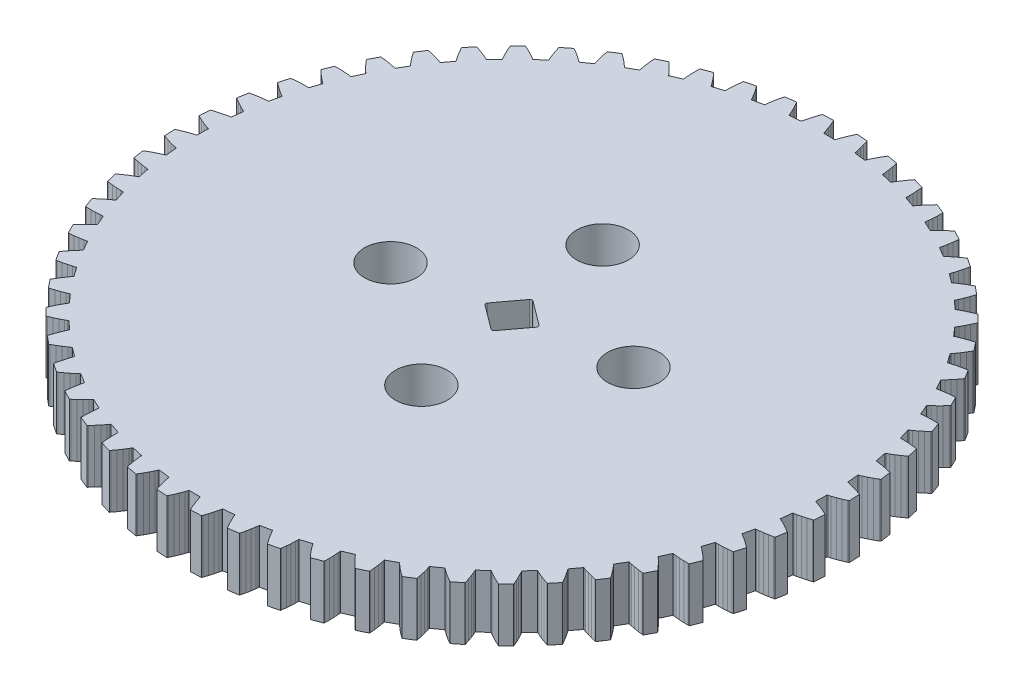
SolidWorks part; units mm, degrees
ref_plane "Front Plane" through (0, 0, 0) normal (0, 0, 1) x (1, 0, 0)
ref_plane "Top Plane" through (0, 0, 0) normal (0, 1, 0) x (1, 0, 0)
ref_plane "Right Plane" through (0, 0, 0) normal (1, 0, 0) x (0, 0, -1)
sketch "Sketch2" plane through (0, 0, 0) normal (0, 1, 0) x (1, 0, 0)
  line L0 (1.5877, 28.5868) -> (1.4918, 28.6064)
  line L1 (1.4918, 28.6064) -> (1.2998, 28.6492)
  line L2 (1.2998, 28.6492) -> (0.9152, 28.7484)
  line L3 (0.9152, 28.7484) -> (0.53, 28.8645)
  line L4 (0.53, 28.8645) -> (0.1446, 28.9962)
  line L5 (0.1446, 28.9962) -> (0.0483, 29.0314)
  line L6 (0.0483, 29.0314) -> (0.0085, 30.0293)
  line L7 (0.0085, 30.0293) -> (0.1018, 30.0721)
  line L8 (0.1018, 30.0721) -> (0.4755, 30.234)
  line L9 (0.4755, 30.234) -> (0.8502, 30.3803)
  line L10 (0.8502, 30.3803) -> (1.2257, 30.5098)
  line L11 (1.2257, 30.5098) -> (1.4137, 30.5678)
  line L12 (1.4137, 30.5678) -> (1.5078, 30.5949)
  line L13 (1.5078, 30.5949) -> (1.521, 31.6473)
  line L14 (1.521, 31.6473) -> (1.4277, 31.6768)
  line L15 (1.4277, 31.6768) -> (1.2412, 31.7395)
  line L16 (1.2412, 31.7395) -> (0.869, 31.8784)
  line L17 (0.869, 31.8784) -> (0.4981, 32.034)
  line L18 (0.4981, 32.034) -> (0.1286, 32.2053)
  line L19 (0.1286, 32.2053) -> (0.0365, 32.2505)
  line L20 (0.0365, 32.2505) -> (0.1012, 33.247)
  line L21 (0.1012, 33.247) -> (0.1984, 33.2798)
  line L22 (0.1984, 33.2798) -> (0.587, 33.4018)
  line L23 (0.587, 33.4018) -> (0.975, 33.5081)
  line L24 (0.975, 33.5081) -> (1.362, 33.5977)
  line L25 (1.362, 33.5977) -> (1.555, 33.6356)
  line L26 (1.555, 33.6356) -> (1.6514, 33.6528)
  line L27 (1.6514, 33.6528) -> (1.7745, 34.6981)
  line L28 (1.7745, 34.6981) -> (1.6848, 34.7372)
  line L29 (1.6848, 34.7372) -> (1.5059, 34.819)
  line L30 (1.5059, 34.819) -> (1.1503, 34.996)
  line L31 (1.1503, 34.996) -> (0.7977, 35.1896)
  line L32 (0.7977, 35.1896) -> (0.4481, 35.3986)
  line L33 (0.4481, 35.3986) -> (0.3612, 35.4531)
  line L34 (0.3612, 35.4531) -> (0.5298, 36.4374)
  line L35 (0.5298, 36.4374) -> (0.6299, 36.4599)
  line L36 (0.6299, 36.4599) -> (1.0291, 36.5406)
  line L37 (1.0291, 36.5406) -> (1.4261, 36.6058)
  line L38 (1.4261, 36.6058) -> (1.8203, 36.6544)
  line L39 (1.8203, 36.6544) -> (2.0162, 36.672)
  line L40 (2.0162, 36.672) -> (2.1139, 36.679)
  line L41 (2.1139, 36.679) -> (2.3456, 37.7056)
  line L42 (2.3456, 37.7056) -> (2.2604, 37.7539)
  line L43 (2.2604, 37.7539) -> (2.0911, 37.8539)
  line L44 (2.0911, 37.8539) -> (1.7559, 38.0672)
  line L45 (1.7559, 38.0672) -> (1.4255, 38.2965)
  line L46 (1.4255, 38.2965) -> (1.0996, 38.5409)
  line L47 (1.0996, 38.5409) -> (1.0189, 38.6042)
  line L48 (1.0189, 38.6042) -> (1.2894, 39.5655)
  line L49 (1.2894, 39.5655) -> (1.3914, 39.5774)
  line L50 (1.3914, 39.5774) -> (1.7968, 39.6159)
  line L51 (1.7968, 39.6159) -> (2.1984, 39.6393)
  line L52 (2.1984, 39.6393) -> (2.5956, 39.6464)
  line L53 (2.5956, 39.6464) -> (2.7923, 39.6434)
  line L54 (2.7923, 39.6434) -> (2.8901, 39.6402)
  line L55 (2.8901, 39.6402) -> (3.2279, 40.637)
  line L56 (3.2279, 40.637) -> (3.1482, 40.6939)
  line L57 (3.1482, 40.6939) -> (2.9903, 40.8111)
  line L58 (2.9903, 40.8111) -> (2.6792, 41.0582)
  line L59 (2.6792, 41.0582) -> (2.3746, 41.3209)
  line L60 (2.3746, 41.3209) -> (2.0761, 41.5979)
  line L61 (2.0761, 41.5979) -> (2.0024, 41.6694)
  line L62 (2.0024, 41.6694) -> (2.372, 42.5971)
  line L63 (2.372, 42.5971) -> (2.4746, 42.5983)
  line L64 (2.4746, 42.5983) -> (2.8818, 42.5942)
  line L65 (2.8818, 42.5942) -> (3.2836, 42.5754)
  line L66 (3.2836, 42.5754) -> (3.6794, 42.541)
  line L67 (3.6794, 42.541) -> (3.8747, 42.5175)
  line L68 (3.8747, 42.5175) -> (3.9716, 42.504)
  line L69 (3.9716, 42.504) -> (4.4118, 43.4601)
  line L70 (4.4118, 43.4601) -> (4.3385, 43.525)
  line L71 (4.3385, 43.525) -> (4.1936, 43.6581)
  line L72 (4.1936, 43.6581) -> (3.9102, 43.9363)
  line L73 (3.9102, 43.9363) -> (3.6346, 44.2294)
  line L74 (3.6346, 44.2294) -> (3.3667, 44.5362)
  line L75 (3.3667, 44.5362) -> (3.3009, 44.6149)
  line L76 (3.3009, 44.6149) -> (3.7654, 45.4989)
  line L77 (3.7654, 45.4989) -> (3.8676, 45.4893)
  line L78 (3.8676, 45.4893) -> (4.2722, 45.4427)
  line L79 (4.2722, 45.4427) -> (4.6698, 45.3821)
  line L80 (4.6698, 45.3821) -> (5.0598, 45.3065)
  line L81 (5.0598, 45.3065) -> (5.2516, 45.2627)
  line L82 (5.2516, 45.2627) -> (5.3466, 45.2391)
  line L83 (5.3466, 45.2391) -> (5.8842, 46.1439)
  line L84 (5.8842, 46.1439) -> (5.8182, 46.2162)
  line L85 (5.8182, 46.2162) -> (5.688, 46.3637)
  line L86 (5.688, 46.3637) -> (5.4352, 46.67)
  line L87 (5.4352, 46.67) -> (5.1918, 46.9903)
  line L88 (5.1918, 46.9903) -> (4.9574, 47.3234)
  line L89 (4.9574, 47.3234) -> (4.9002, 47.4085)
  line L90 (4.9002, 47.4085) -> (5.4545, 48.2392)
  line L91 (5.4545, 48.2392) -> (5.5552, 48.219)
  line L92 (5.5552, 48.219) -> (5.9527, 48.1303)
  line L93 (5.9527, 48.1303) -> (6.3418, 48.0284)
  line L94 (6.3418, 48.0284) -> (6.7217, 47.9125)
  line L95 (6.7217, 47.9125) -> (6.9079, 47.8489)
  line L96 (6.9079, 47.8489) -> (6.9999, 47.8156)
  line L97 (6.9999, 47.8156) -> (7.6292, 48.6592)
  line L98 (7.6292, 48.6592) -> (7.571, 48.7379)
  line L99 (7.571, 48.7379) -> (7.457, 48.8982)
  line L100 (7.457, 48.8982) -> (7.2376, 49.2293)
  line L101 (7.2376, 49.2293) -> (7.029, 49.5733)
  line L102 (7.029, 49.5733) -> (6.8307, 49.929)
  line L103 (6.8307, 49.929) -> (6.7827, 50.0197)
  line L104 (6.7827, 50.0197) -> (7.4209, 50.7878)
  line L105 (7.4209, 50.7878) -> (7.5188, 50.7573)
  line L106 (7.5188, 50.7573) -> (7.9049, 50.6275)
  line L107 (7.9049, 50.6275) -> (8.2812, 50.4855)
  line L108 (8.2812, 50.4855) -> (8.647, 50.3305)
  line L109 (8.647, 50.3305) -> (8.8254, 50.2478)
  line L110 (8.8254, 50.2478) -> (8.9135, 50.205)
  line L111 (8.9135, 50.205) -> (9.6275, 50.9783)
  line L112 (9.6275, 50.9783) -> (9.5779, 51.0626)
  line L113 (9.5779, 51.0626) -> (9.4812, 51.234)
  line L114 (9.4812, 51.234) -> (9.2976, 51.5862)
  line L115 (9.2976, 51.5862) -> (9.1262, 51.9501)
  line L116 (9.1262, 51.9501) -> (8.9662, 52.3246)
  line L117 (8.9662, 52.3246) -> (8.9279, 52.4198)
  line L118 (8.9279, 52.4198) -> (9.6428, 53.117)
  line L119 (9.6428, 53.117) -> (9.737, 53.0764)
  line L120 (9.737, 53.0764) -> (10.1075, 52.907)
  line L121 (10.1075, 52.907) -> (10.4669, 52.7265)
  line L122 (10.4669, 52.7265) -> (10.8144, 52.534)
  line L123 (10.8144, 52.534) -> (10.9833, 52.4331)
  line L124 (10.9833, 52.4331) -> (11.0664, 52.3814)
  line L125 (11.0664, 52.3814) -> (11.8573, 53.0757)
  line L126 (11.8573, 53.0757) -> (11.8168, 53.1649)
  line L127 (11.8168, 53.1649) -> (11.7386, 53.3454)
  line L128 (11.7386, 53.3454) -> (11.5928, 53.7148)
  line L129 (11.5928, 53.7148) -> (11.4603, 54.0947)
  line L130 (11.4603, 54.0947) -> (11.3403, 54.4839)
  line L131 (11.3403, 54.4839) -> (11.3122, 54.5826)
  line L132 (11.3122, 54.5826) -> (12.0961, 55.2012)
  line L133 (12.0961, 55.2012) -> (12.1855, 55.1509)
  line L134 (12.1855, 55.1509) -> (12.5362, 54.9438)
  line L135 (12.5362, 54.9438) -> (12.8748, 54.7266)
  line L136 (12.8748, 54.7266) -> (13.2003, 54.499)
  line L137 (13.2003, 54.499) -> (13.3577, 54.3809)
  line L138 (13.3577, 54.3809) -> (13.4349, 54.3208)
  line L139 (13.4349, 54.3208) -> (14.2941, 54.9287)
  line L140 (14.2941, 54.9287) -> (14.2631, 55.0215)
  line L141 (14.2631, 55.0215) -> (14.2042, 55.2092)
  line L142 (14.2042, 55.2092) -> (14.0978, 55.5919)
  line L143 (14.0978, 55.5919) -> (14.0058, 55.9835)
  line L144 (14.0058, 55.9835) -> (13.9271, 56.3831)
  line L145 (13.9271, 56.3831) -> (13.9095, 56.4842)
  line L146 (13.9095, 56.4842) -> (14.7538, 57.0175)
  line L147 (14.7538, 57.0175) -> (14.8375, 56.9582)
  line L148 (14.8375, 56.9582) -> (15.1646, 56.7155)
  line L149 (15.1646, 56.7155) -> (15.4786, 56.4641)
  line L150 (15.4786, 56.4641) -> (15.7785, 56.2037)
  line L151 (15.7785, 56.2037) -> (15.9227, 56.0699)
  line L152 (15.9227, 56.0699) -> (15.9932, 56.002)
  line L153 (15.9932, 56.002) -> (16.9112, 56.5167)
  line L154 (16.9112, 56.5167) -> (16.8901, 56.6123)
  line L155 (16.8901, 56.6123) -> (16.8512, 56.8051)
  line L156 (16.8512, 56.8051) -> (16.7854, 57.1969)
  line L157 (16.7854, 57.1969) -> (16.7347, 57.5959)
  line L158 (16.7347, 57.5959) -> (16.6983, 58.0016)
  line L159 (16.6983, 58.0016) -> (16.6913, 58.104)
  line L160 (16.6913, 58.104) -> (17.5867, 58.5461)
  line L161 (17.5867, 58.5461) -> (17.6638, 58.4783)
  line L162 (17.6638, 58.4783) -> (17.9637, 58.2028)
  line L163 (17.9637, 58.2028) -> (18.2498, 57.92)
  line L164 (18.2498, 57.92) -> (18.5208, 57.6296)
  line L165 (18.5208, 57.6296) -> (18.6502, 57.4814)
  line L166 (18.6502, 57.4814) -> (18.7133, 57.4066)
  line L167 (18.7133, 57.4066) -> (19.6801, 57.8225)
  line L168 (19.6801, 57.8225) -> (19.6691, 57.9198)
  line L169 (19.6691, 57.9198) -> (19.6504, 58.1156)
  line L170 (19.6504, 58.1156) -> (19.626, 58.5121)
  line L171 (19.626, 58.5121) -> (19.6173, 58.9143)
  line L172 (19.6173, 58.9143) -> (19.6235, 59.3215)
  line L173 (19.6235, 59.3215) -> (19.6273, 59.4241)
  line L174 (19.6273, 59.4241) -> (20.5639, 59.7702)
  line L175 (20.5639, 59.7702) -> (20.6335, 59.6947)
  line L176 (20.6335, 59.6947) -> (20.903, 59.3893)
  line L177 (20.903, 59.3893) -> (21.1579, 59.0782)
  line L178 (21.1579, 59.0782) -> (21.3971, 58.7611)
  line L179 (21.3971, 58.7611) -> (21.5103, 58.6002)
  line L180 (21.5103, 58.6002) -> (21.5652, 58.5191)
  line L181 (21.5652, 58.5191) -> (22.5702, 58.8317)
  line L182 (22.5702, 58.8317) -> (22.5694, 58.9296)
  line L183 (22.5694, 58.9296) -> (22.5714, 59.1264)
  line L184 (22.5714, 59.1264) -> (22.5885, 59.5232)
  line L185 (22.5885, 59.5232) -> (22.6219, 59.9241)
  line L186 (22.6219, 59.9241) -> (22.6706, 60.3284)
  line L187 (22.6706, 60.3284) -> (22.6851, 60.43)
  line L188 (22.6851, 60.43) -> (23.6528, 60.6763)
  line L189 (23.6528, 60.6763) -> (23.7141, 60.594)
  line L190 (23.7141, 60.594) -> (23.9502, 60.2621)
  line L191 (23.9502, 60.2621) -> (24.1712, 59.926)
  line L192 (24.1712, 59.926) -> (24.3759, 59.5857)
  line L193 (24.3759, 59.5857) -> (24.4717, 59.4138)
  line L194 (24.4717, 59.4138) -> (24.5178, 59.3275)
  line L195 (24.5178, 59.3275) -> (25.55, 59.5333)
  line L196 (25.55, 59.5333) -> (25.5594, 59.6308)
  line L197 (25.5594, 59.6308) -> (25.5819, 59.8262)
  line L198 (25.5819, 59.8262) -> (25.6404, 60.2191)
  line L199 (25.6404, 60.2191) -> (25.7156, 60.6143)
  line L200 (25.7156, 60.6143) -> (25.8063, 61.0113)
  line L201 (25.8063, 61.0113) -> (25.8313, 61.1108)
  line L202 (25.8313, 61.1108) -> (26.8195, 61.2547)
  line L203 (26.8195, 61.2547) -> (26.8718, 61.1664)
  line L204 (26.8718, 61.1664) -> (27.0719, 60.8117)
  line L205 (27.0719, 60.8117) -> (27.2566, 60.4543)
  line L206 (27.2566, 60.4543) -> (27.4246, 60.0944)
  line L207 (27.4246, 60.0944) -> (27.5019, 59.9135)
  line L208 (27.5019, 59.9135) -> (27.5388, 59.8228)
  line L209 (27.5388, 59.8228) -> (28.5868, 59.9196)
  line L210 (28.5868, 59.9196) -> (28.6064, 60.0155)
  line L211 (28.6064, 60.0155) -> (28.6492, 60.2075)
  line L212 (28.6492, 60.2075) -> (28.7484, 60.5922)
  line L213 (28.7484, 60.5922) -> (28.8645, 60.9773)
  line L214 (28.8645, 60.9773) -> (28.9962, 61.3627)
  line L215 (28.9962, 61.3627) -> (29.0314, 61.4591)
  line L216 (29.0314, 61.4591) -> (30.0293, 61.4988)
  line L217 (30.0293, 61.4988) -> (30.0721, 61.4055)
  line L218 (30.0721, 61.4055) -> (30.234, 61.0318)
  line L219 (30.234, 61.0318) -> (30.3803, 60.6571)
  line L220 (30.3803, 60.6571) -> (30.5098, 60.2816)
  line L221 (30.5098, 60.2816) -> (30.5678, 60.0936)
  line L222 (30.5678, 60.0936) -> (30.5949, 59.9996)
  line L223 (30.5949, 59.9996) -> (31.6473, 59.9863)
  line L224 (31.6473, 59.9863) -> (31.6768, 60.0797)
  line L225 (31.6768, 60.0797) -> (31.7395, 60.2662)
  line L226 (31.7395, 60.2662) -> (31.8784, 60.6383)
  line L227 (31.8784, 60.6383) -> (32.034, 61.0092)
  line L228 (32.034, 61.0092) -> (32.2053, 61.3787)
  line L229 (32.2053, 61.3787) -> (32.2505, 61.4709)
  line L230 (32.2505, 61.4709) -> (33.247, 61.4061)
  line L231 (33.247, 61.4061) -> (33.2798, 61.3089)
  line L232 (33.2798, 61.3089) -> (33.4018, 60.9203)
  line L233 (33.4018, 60.9203) -> (33.5081, 60.5323)
  line L234 (33.5081, 60.5323) -> (33.5977, 60.1454)
  line L235 (33.5977, 60.1454) -> (33.6356, 59.9523)
  line L236 (33.6356, 59.9523) -> (33.6528, 59.8559)
  line L237 (33.6528, 59.8559) -> (34.6981, 59.7328)
  line L238 (34.6981, 59.7328) -> (34.7372, 59.8225)
  line L239 (34.7372, 59.8225) -> (34.819, 60.0014)
  line L240 (34.819, 60.0014) -> (34.996, 60.357)
  line L241 (34.996, 60.357) -> (35.1896, 60.7096)
  line L242 (35.1896, 60.7096) -> (35.3986, 61.0592)
  line L243 (35.3986, 61.0592) -> (35.4531, 61.1462)
  line L244 (35.4531, 61.1462) -> (36.4374, 60.9776)
  line L245 (36.4374, 60.9776) -> (36.4599, 60.8774)
  line L246 (36.4599, 60.8774) -> (36.5406, 60.4782)
  line L247 (36.5406, 60.4782) -> (36.6058, 60.0813)
  line L248 (36.6058, 60.0813) -> (36.6544, 59.6871)
  line L249 (36.6544, 59.6871) -> (36.672, 59.4911)
  line L250 (36.672, 59.4911) -> (36.679, 59.3935)
  line L251 (36.679, 59.3935) -> (37.7056, 59.1617)
  line L252 (37.7056, 59.1617) -> (37.7539, 59.2469)
  line L253 (37.7539, 59.2469) -> (37.8539, 59.4163)
  line L254 (37.8539, 59.4163) -> (38.0672, 59.7514)
  line L255 (38.0672, 59.7514) -> (38.2965, 60.0819)
  line L256 (38.2965, 60.0819) -> (38.5409, 60.4077)
  line L257 (38.5409, 60.4077) -> (38.6042, 60.4884)
  line L258 (38.6042, 60.4884) -> (39.5655, 60.2179)
  line L259 (39.5655, 60.2179) -> (39.5774, 60.116)
  line L260 (39.5774, 60.116) -> (39.6159, 59.7105)
  line L261 (39.6159, 59.7105) -> (39.6393, 59.3089)
  line L262 (39.6393, 59.3089) -> (39.6464, 58.9118)
  line L263 (39.6464, 58.9118) -> (39.6434, 58.7151)
  line L264 (39.6434, 58.7151) -> (39.6402, 58.6172)
  line L265 (39.6402, 58.6172) -> (40.637, 58.2794)
  line L266 (40.637, 58.2794) -> (40.6939, 58.3591)
  line L267 (40.6939, 58.3591) -> (40.8111, 58.5171)
  line L268 (40.8111, 58.5171) -> (41.0582, 58.8281)
  line L269 (41.0582, 58.8281) -> (41.3209, 59.1328)
  line L270 (41.3209, 59.1328) -> (41.5979, 59.4313)
  line L271 (41.5979, 59.4313) -> (41.6694, 59.5049)
  line L272 (41.6694, 59.5049) -> (42.5971, 59.1354)
  line L273 (42.5971, 59.1354) -> (42.5983, 59.0328)
  line L274 (42.5983, 59.0328) -> (42.5942, 58.6255)
  line L275 (42.5942, 58.6255) -> (42.5754, 58.2237)
  line L276 (42.5754, 58.2237) -> (42.541, 57.828)
  line L277 (42.541, 57.828) -> (42.5175, 57.6327)
  line L278 (42.5175, 57.6327) -> (42.504, 57.5357)
  line L279 (42.504, 57.5357) -> (43.4601, 57.0956)
  line L280 (43.4601, 57.0956) -> (43.525, 57.1688)
  line L281 (43.525, 57.1688) -> (43.6581, 57.3137)
  line L282 (43.6581, 57.3137) -> (43.9363, 57.5972)
  line L283 (43.9363, 57.5972) -> (44.2294, 57.8727)
  line L284 (44.2294, 57.8727) -> (44.5362, 58.1406)
  line L285 (44.5362, 58.1406) -> (44.6149, 58.2064)
  line L286 (44.6149, 58.2064) -> (45.4989, 57.7419)
  line L287 (45.4989, 57.7419) -> (45.4893, 57.6398)
  line L288 (45.4893, 57.6398) -> (45.4427, 57.2351)
  line L289 (45.4427, 57.2351) -> (45.3821, 56.8375)
  line L290 (45.3821, 56.8375) -> (45.3065, 56.4475)
  line L291 (45.3065, 56.4475) -> (45.2627, 56.2558)
  line L292 (45.2627, 56.2558) -> (45.2391, 56.1607)
  line L293 (45.2391, 56.1607) -> (46.1439, 55.6231)
  line L294 (46.1439, 55.6231) -> (46.2162, 55.6892)
  line L295 (46.2162, 55.6892) -> (46.3637, 55.8193)
  line L296 (46.3637, 55.8193) -> (46.67, 56.0722)
  line L297 (46.67, 56.0722) -> (46.9903, 56.3156)
  line L298 (46.9903, 56.3156) -> (47.3234, 56.5499)
  line L299 (47.3234, 56.5499) -> (47.4085, 56.6072)
  line L300 (47.4085, 56.6072) -> (48.2392, 56.0528)
  line L301 (48.2392, 56.0528) -> (48.219, 55.9522)
  line L302 (48.219, 55.9522) -> (48.1303, 55.5547)
  line L303 (48.1303, 55.5547) -> (48.0284, 55.1655)
  line L304 (48.0284, 55.1655) -> (47.9125, 54.7856)
  line L305 (47.9125, 54.7856) -> (47.8489, 54.5995)
  line L306 (47.8489, 54.5995) -> (47.8156, 54.5074)
  line L307 (47.8156, 54.5074) -> (48.6592, 53.8781)
  line L308 (48.6592, 53.8781) -> (48.7379, 53.9363)
  line L309 (48.7379, 53.9363) -> (48.8982, 54.0503)
  line L310 (48.8982, 54.0503) -> (49.2293, 54.2698)
  line L311 (49.2293, 54.2698) -> (49.5733, 54.4783)
  line L312 (49.5733, 54.4783) -> (49.929, 54.6766)
  line L313 (49.929, 54.6766) -> (50.0197, 54.7246)
  line L314 (50.0197, 54.7246) -> (50.7878, 54.0865)
  line L315 (50.7878, 54.0865) -> (50.7573, 53.9885)
  line L316 (50.7573, 53.9885) -> (50.6275, 53.6024)
  line L317 (50.6275, 53.6024) -> (50.4855, 53.2261)
  line L318 (50.4855, 53.2261) -> (50.3305, 52.8604)
  line L319 (50.3305, 52.8604) -> (50.2478, 52.6819)
  line L320 (50.2478, 52.6819) -> (50.205, 52.5938)
  line L321 (50.205, 52.5938) -> (50.9783, 51.8798)
  line L322 (50.9783, 51.8798) -> (51.0626, 51.9294)
  line L323 (51.0626, 51.9294) -> (51.234, 52.0261)
  line L324 (51.234, 52.0261) -> (51.5862, 52.2097)
  line L325 (51.5862, 52.2097) -> (51.9501, 52.3812)
  line L326 (51.9501, 52.3812) -> (52.3246, 52.5412)
  line L327 (52.3246, 52.5412) -> (52.4198, 52.5795)
  line L328 (52.4198, 52.5795) -> (53.117, 51.8645)
  line L329 (53.117, 51.8645) -> (53.0764, 51.7703)
  line L330 (53.0764, 51.7703) -> (52.907, 51.3999)
  line L331 (52.907, 51.3999) -> (52.7265, 51.0404)
  line L332 (52.7265, 51.0404) -> (52.534, 50.6929)
  line L333 (52.534, 50.6929) -> (52.4331, 50.5241)
  line L334 (52.4331, 50.5241) -> (52.3814, 50.441)
  line L335 (52.3814, 50.441) -> (53.0757, 49.65)
  line L336 (53.0757, 49.65) -> (53.1649, 49.6906)
  line L337 (53.1649, 49.6906) -> (53.3454, 49.7688)
  line L338 (53.3454, 49.7688) -> (53.7148, 49.9146)
  line L339 (53.7148, 49.9146) -> (54.0947, 50.0471)
  line L340 (54.0947, 50.0471) -> (54.4839, 50.1671)
  line L341 (54.4839, 50.1671) -> (54.5826, 50.1952)
  line L342 (54.5826, 50.1952) -> (55.2012, 49.4113)
  line L343 (55.2012, 49.4113) -> (55.1509, 49.3218)
  line L344 (55.1509, 49.3218) -> (54.9438, 48.9711)
  line L345 (54.9438, 48.9711) -> (54.7266, 48.6325)
  line L346 (54.7266, 48.6325) -> (54.499, 48.307)
  line L347 (54.499, 48.307) -> (54.3809, 48.1497)
  line L348 (54.3809, 48.1497) -> (54.3208, 48.0724)
  line L349 (54.3208, 48.0724) -> (54.9287, 47.2132)
  line L350 (54.9287, 47.2132) -> (55.0215, 47.2442)
  line L351 (55.0215, 47.2442) -> (55.2092, 47.3031)
  line L352 (55.2092, 47.3031) -> (55.5919, 47.4095)
  line L353 (55.5919, 47.4095) -> (55.9835, 47.5016)
  line L354 (55.9835, 47.5016) -> (56.3831, 47.5802)
  line L355 (56.3831, 47.5802) -> (56.4842, 47.5979)
  line L356 (56.4842, 47.5979) -> (57.0175, 46.7536)
  line L357 (57.0175, 46.7536) -> (56.9582, 46.6699)
  line L358 (56.9582, 46.6699) -> (56.7155, 46.3428)
  line L359 (56.7155, 46.3428) -> (56.4641, 46.0287)
  line L360 (56.4641, 46.0287) -> (56.2037, 45.7288)
  line L361 (56.2037, 45.7288) -> (56.0699, 45.5846)
  line L362 (56.0699, 45.5846) -> (56.002, 45.5141)
  line L363 (56.002, 45.5141) -> (56.5167, 44.5961)
  line L364 (56.5167, 44.5961) -> (56.6123, 44.6172)
  line L365 (56.6123, 44.6172) -> (56.8051, 44.6562)
  line L366 (56.8051, 44.6562) -> (57.1969, 44.722)
  line L367 (57.1969, 44.722) -> (57.5959, 44.7726)
  line L368 (57.5959, 44.7726) -> (58.0016, 44.809)
  line L369 (58.0016, 44.809) -> (58.104, 44.816)
  line L370 (58.104, 44.816) -> (58.5461, 43.9206)
  line L371 (58.5461, 43.9206) -> (58.4783, 43.8436)
  line L372 (58.4783, 43.8436) -> (58.2028, 43.5436)
  line L373 (58.2028, 43.5436) -> (57.92, 43.2576)
  line L374 (57.92, 43.2576) -> (57.6296, 42.9865)
  line L375 (57.6296, 42.9865) -> (57.4814, 42.8571)
  line L376 (57.4814, 42.8571) -> (57.4066, 42.7941)
  line L377 (57.4066, 42.7941) -> (57.8225, 41.8273)
  line L378 (57.8225, 41.8273) -> (57.9198, 41.8383)
  line L379 (57.9198, 41.8383) -> (58.1156, 41.8569)
  line L380 (58.1156, 41.8569) -> (58.5121, 41.8814)
  line L381 (58.5121, 41.8814) -> (58.9143, 41.89)
  line L382 (58.9143, 41.89) -> (59.3215, 41.8839)
  line L383 (59.3215, 41.8839) -> (59.4241, 41.8801)
  line L384 (59.4241, 41.8801) -> (59.7702, 40.9434)
  line L385 (59.7702, 40.9434) -> (59.6947, 40.8738)
  line L386 (59.6947, 40.8738) -> (59.3893, 40.6043)
  line L387 (59.3893, 40.6043) -> (59.0782, 40.3494)
  line L388 (59.0782, 40.3494) -> (58.7611, 40.1102)
  line L389 (58.7611, 40.1102) -> (58.6002, 39.997)
  line L390 (58.6002, 39.997) -> (58.5191, 39.9421)
  line L391 (58.5191, 39.9421) -> (58.8317, 38.9372)
  line L392 (58.8317, 38.9372) -> (58.9296, 38.9379)
  line L393 (58.9296, 38.9379) -> (59.1264, 38.936)
  line L394 (59.1264, 38.936) -> (59.5232, 38.9189)
  line L395 (59.5232, 38.9189) -> (59.9241, 38.8854)
  line L396 (59.9241, 38.8854) -> (60.3284, 38.8367)
  line L397 (60.3284, 38.8367) -> (60.43, 38.8223)
  line L398 (60.43, 38.8223) -> (60.6763, 37.8545)
  line L399 (60.6763, 37.8545) -> (60.594, 37.7932)
  line L400 (60.594, 37.7932) -> (60.2621, 37.5571)
  line L401 (60.2621, 37.5571) -> (59.926, 37.3361)
  line L402 (59.926, 37.3361) -> (59.5857, 37.1314)
  line L403 (59.5857, 37.1314) -> (59.4138, 37.0356)
  line L404 (59.4138, 37.0356) -> (59.3275, 36.9895)
  line L405 (59.3275, 36.9895) -> (59.5333, 35.9574)
  line L406 (59.5333, 35.9574) -> (59.6308, 35.9479)
  line L407 (59.6308, 35.9479) -> (59.8262, 35.9254)
  line L408 (59.8262, 35.9254) -> (60.2191, 35.8669)
  line L409 (60.2191, 35.8669) -> (60.6143, 35.7918)
  line L410 (60.6143, 35.7918) -> (61.0113, 35.7011)
  line L411 (61.0113, 35.7011) -> (61.1108, 35.676)
  line L412 (61.1108, 35.676) -> (61.2547, 34.6878)
  line L413 (61.2547, 34.6878) -> (61.1664, 34.6355)
  line L414 (61.1664, 34.6355) -> (60.8117, 34.4354)
  line L415 (60.8117, 34.4354) -> (60.4543, 34.2507)
  line L416 (60.4543, 34.2507) -> (60.0944, 34.0827)
  line L417 (60.0944, 34.0827) -> (59.9135, 34.0054)
  line L418 (59.9135, 34.0054) -> (59.8228, 33.9686)
  line L419 (59.8228, 33.9686) -> (59.9196, 32.9206)
  line L420 (59.9196, 32.9206) -> (60.0155, 32.901)
  line L421 (60.0155, 32.901) -> (60.2075, 32.8582)
  line L422 (60.2075, 32.8582) -> (60.5922, 32.7589)
  line L423 (60.5922, 32.7589) -> (60.9773, 32.6429)
  line L424 (60.9773, 32.6429) -> (61.3627, 32.5112)
  line L425 (61.3627, 32.5112) -> (61.4591, 32.4759)
  line L426 (61.4591, 32.4759) -> (61.4988, 31.4781)
  line L427 (61.4988, 31.4781) -> (61.4055, 31.4352)
  line L428 (61.4055, 31.4352) -> (61.0318, 31.2733)
  line L429 (61.0318, 31.2733) -> (60.6571, 31.127)
  line L430 (60.6571, 31.127) -> (60.2816, 30.9975)
  line L431 (60.2816, 30.9975) -> (60.0936, 30.9396)
  line L432 (60.0936, 30.9396) -> (59.9996, 30.9124)
  line L433 (59.9996, 30.9124) -> (59.9863, 29.86)
  line L434 (59.9863, 29.86) -> (60.0797, 29.8305)
  line L435 (60.0797, 29.8305) -> (60.2662, 29.7678)
  line L436 (60.2662, 29.7678) -> (60.6383, 29.629)
  line L437 (60.6383, 29.629) -> (61.0092, 29.4733)
  line L438 (61.0092, 29.4733) -> (61.3787, 29.302)
  line L439 (61.3787, 29.302) -> (61.4709, 29.2569)
  line L440 (61.4709, 29.2569) -> (61.4061, 28.2604)
  line L441 (61.4061, 28.2604) -> (61.3089, 28.2275)
  line L442 (61.3089, 28.2275) -> (60.9203, 28.1055)
  line L443 (60.9203, 28.1055) -> (60.5323, 27.9992)
  line L444 (60.5323, 27.9992) -> (60.1454, 27.9097)
  line L445 (60.1454, 27.9097) -> (59.9523, 27.8717)
  line L446 (59.9523, 27.8717) -> (59.8559, 27.8545)
  line L447 (59.8559, 27.8545) -> (59.7328, 26.8093)
  line L448 (59.7328, 26.8093) -> (59.8225, 26.7702)
  line L449 (59.8225, 26.7702) -> (60.0014, 26.6884)
  line L450 (60.0014, 26.6884) -> (60.357, 26.5113)
  line L451 (60.357, 26.5113) -> (60.7096, 26.3178)
  line L452 (60.7096, 26.3178) -> (61.0592, 26.1088)
  line L453 (61.0592, 26.1088) -> (61.1462, 26.0542)
  line L454 (61.1462, 26.0542) -> (60.9776, 25.07)
  line L455 (60.9776, 25.07) -> (60.8774, 25.0475)
  line L456 (60.8774, 25.0475) -> (60.4782, 24.9668)
  line L457 (60.4782, 24.9668) -> (60.0813, 24.9016)
  line L458 (60.0813, 24.9016) -> (59.6871, 24.853)
  line L459 (59.6871, 24.853) -> (59.4911, 24.8354)
  line L460 (59.4911, 24.8354) -> (59.3935, 24.8284)
  line L461 (59.3935, 24.8284) -> (59.1617, 23.8017)
  line L462 (59.1617, 23.8017) -> (59.2469, 23.7535)
  line L463 (59.2469, 23.7535) -> (59.4163, 23.6534)
  line L464 (59.4163, 23.6534) -> (59.7514, 23.4402)
  line L465 (59.7514, 23.4402) -> (60.0819, 23.2108)
  line L466 (60.0819, 23.2108) -> (60.4077, 22.9664)
  line L467 (60.4077, 22.9664) -> (60.4884, 22.9031)
  line L468 (60.4884, 22.9031) -> (60.2179, 21.9418)
  line L469 (60.2179, 21.9418) -> (60.116, 21.9299)
  line L470 (60.116, 21.9299) -> (59.7105, 21.8914)
  line L471 (59.7105, 21.8914) -> (59.3089, 21.8681)
  line L472 (59.3089, 21.8681) -> (58.9118, 21.8609)
  line L473 (58.9118, 21.8609) -> (58.7151, 21.8639)
  line L474 (58.7151, 21.8639) -> (58.6172, 21.8672)
  line L475 (58.6172, 21.8672) -> (58.2794, 20.8704)
  line L476 (58.2794, 20.8704) -> (58.3591, 20.8134)
  line L477 (58.3591, 20.8134) -> (58.5171, 20.6962)
  line L478 (58.5171, 20.6962) -> (58.8281, 20.4491)
  line L479 (58.8281, 20.4491) -> (59.1328, 20.1865)
  line L480 (59.1328, 20.1865) -> (59.4313, 19.9094)
  line L481 (59.4313, 19.9094) -> (59.5049, 19.838)
  line L482 (59.5049, 19.838) -> (59.1354, 18.9103)
  line L483 (59.1354, 18.9103) -> (59.0328, 18.9091)
  line L484 (59.0328, 18.9091) -> (58.6255, 18.9131)
  line L485 (58.6255, 18.9131) -> (58.2237, 18.9319)
  line L486 (58.2237, 18.9319) -> (57.828, 18.9663)
  line L487 (57.828, 18.9663) -> (57.6327, 18.9899)
  line L488 (57.6327, 18.9899) -> (57.5357, 19.0033)
  line L489 (57.5357, 19.0033) -> (57.0956, 18.0473)
  line L490 (57.0956, 18.0473) -> (57.1688, 17.9824)
  line L491 (57.1688, 17.9824) -> (57.3137, 17.8493)
  line L492 (57.3137, 17.8493) -> (57.5972, 17.571)
  line L493 (57.5972, 17.571) -> (57.8727, 17.278)
  line L494 (57.8727, 17.278) -> (58.1406, 16.9712)
  line L495 (58.1406, 16.9712) -> (58.2064, 16.8925)
  line L496 (58.2064, 16.8925) -> (57.7419, 16.0084)
  line L497 (57.7419, 16.0084) -> (57.6398, 16.018)
  line L498 (57.6398, 16.018) -> (57.2351, 16.0646)
  line L499 (57.2351, 16.0646) -> (56.8375, 16.1253)
  line L500 (56.8375, 16.1253) -> (56.4475, 16.2009)
  line L501 (56.4475, 16.2009) -> (56.2558, 16.2447)
  line L502 (56.2558, 16.2447) -> (56.1607, 16.2682)
  line L503 (56.1607, 16.2682) -> (55.6231, 15.3634)
  line L504 (55.6231, 15.3634) -> (55.6892, 15.2912)
  line L505 (55.6892, 15.2912) -> (55.8193, 15.1437)
  line L506 (55.8193, 15.1437) -> (56.0722, 14.8373)
  line L507 (56.0722, 14.8373) -> (56.3156, 14.5171)
  line L508 (56.3156, 14.5171) -> (56.5499, 14.184)
  line L509 (56.5499, 14.184) -> (56.6072, 14.0988)
  line L510 (56.6072, 14.0988) -> (56.0528, 13.2682)
  line L511 (56.0528, 13.2682) -> (55.9522, 13.2884)
  line L512 (55.9522, 13.2884) -> (55.5547, 13.377)
  line L513 (55.5547, 13.377) -> (55.1655, 13.4789)
  line L514 (55.1655, 13.4789) -> (54.7856, 13.5949)
  line L515 (54.7856, 13.5949) -> (54.5995, 13.6585)
  line L516 (54.5995, 13.6585) -> (54.5074, 13.6918)
  line L517 (54.5074, 13.6918) -> (53.8781, 12.8482)
  line L518 (53.8781, 12.8482) -> (53.9363, 12.7694)
  line L519 (53.9363, 12.7694) -> (54.0503, 12.6091)
  line L520 (54.0503, 12.6091) -> (54.2698, 12.278)
  line L521 (54.2698, 12.278) -> (54.4783, 11.9341)
  line L522 (54.4783, 11.9341) -> (54.6766, 11.5783)
  line L523 (54.6766, 11.5783) -> (54.7246, 11.4876)
  line L524 (54.7246, 11.4876) -> (54.0865, 10.7195)
  line L525 (54.0865, 10.7195) -> (53.9885, 10.7501)
  line L526 (53.9885, 10.7501) -> (53.6024, 10.8798)
  line L527 (53.6024, 10.8798) -> (53.2261, 11.0218)
  line L528 (53.2261, 11.0218) -> (52.8604, 11.1768)
  line L529 (52.8604, 11.1768) -> (52.6819, 11.2596)
  line L530 (52.6819, 11.2596) -> (52.5938, 11.3023)
  line L531 (52.5938, 11.3023) -> (51.8798, 10.5291)
  line L532 (51.8798, 10.5291) -> (51.9294, 10.4447)
  line L533 (51.9294, 10.4447) -> (52.0261, 10.2734)
  line L534 (52.0261, 10.2734) -> (52.2097, 9.9211)
  line L535 (52.2097, 9.9211) -> (52.3812, 9.5573)
  line L536 (52.3812, 9.5573) -> (52.5412, 9.1827)
  line L537 (52.5412, 9.1827) -> (52.5795, 9.0875)
  line L538 (52.5795, 9.0875) -> (51.8645, 8.3903)
  line L539 (51.8645, 8.3903) -> (51.7703, 8.4309)
  line L540 (51.7703, 8.4309) -> (51.3999, 8.6003)
  line L541 (51.3999, 8.6003) -> (51.0404, 8.7809)
  line L542 (51.0404, 8.7809) -> (50.6929, 8.9733)
  line L543 (50.6929, 8.9733) -> (50.5241, 9.0742)
  line L544 (50.5241, 9.0742) -> (50.441, 9.1259)
  line L545 (50.441, 9.1259) -> (49.65, 8.4316)
  line L546 (49.65, 8.4316) -> (49.6906, 8.3425)
  line L547 (49.6906, 8.3425) -> (49.7688, 8.162)
  line L548 (49.7688, 8.162) -> (49.9146, 7.7925)
  line L549 (49.9146, 7.7925) -> (50.0471, 7.4127)
  line L550 (50.0471, 7.4127) -> (50.1671, 7.0235)
  line L551 (50.1671, 7.0235) -> (50.1952, 6.9248)
  line L552 (50.1952, 6.9248) -> (49.4113, 6.3061)
  line L553 (49.4113, 6.3061) -> (49.3218, 6.3564)
  line L554 (49.3218, 6.3564) -> (48.9711, 6.5636)
  line L555 (48.9711, 6.5636) -> (48.6325, 6.7807)
  line L556 (48.6325, 6.7807) -> (48.307, 7.0084)
  line L557 (48.307, 7.0084) -> (48.1497, 7.1264)
  line L558 (48.1497, 7.1264) -> (48.0724, 7.1866)
  line L559 (48.0724, 7.1866) -> (47.2132, 6.5787)
  line L560 (47.2132, 6.5787) -> (47.2442, 6.4858)
  line L561 (47.2442, 6.4858) -> (47.3031, 6.2981)
  line L562 (47.3031, 6.2981) -> (47.4095, 5.9154)
  line L563 (47.4095, 5.9154) -> (47.5016, 5.5238)
  line L564 (47.5016, 5.5238) -> (47.5802, 5.1242)
  line L565 (47.5802, 5.1242) -> (47.5979, 5.0231)
  line L566 (47.5979, 5.0231) -> (46.7536, 4.4898)
  line L567 (46.7536, 4.4898) -> (46.6699, 4.5492)
  line L568 (46.6699, 4.5492) -> (46.3428, 4.7918)
  line L569 (46.3428, 4.7918) -> (46.0287, 5.0432)
  line L570 (46.0287, 5.0432) -> (45.7288, 5.3036)
  line L571 (45.7288, 5.3036) -> (45.5846, 5.4375)
  line L572 (45.5846, 5.4375) -> (45.5141, 5.5053)
  line L573 (45.5141, 5.5053) -> (44.5961, 4.9906)
  line L574 (44.5961, 4.9906) -> (44.6172, 4.895)
  line L575 (44.6172, 4.895) -> (44.6562, 4.7022)
  line L576 (44.6562, 4.7022) -> (44.722, 4.3105)
  line L577 (44.722, 4.3105) -> (44.7726, 3.9114)
  line L578 (44.7726, 3.9114) -> (44.809, 3.5058)
  line L579 (44.809, 3.5058) -> (44.816, 3.4034)
  line L580 (44.816, 3.4034) -> (43.9206, 2.9612)
  line L581 (43.9206, 2.9612) -> (43.8436, 3.029)
  line L582 (43.8436, 3.029) -> (43.5436, 3.3045)
  line L583 (43.5436, 3.3045) -> (43.2576, 3.5873)
  line L584 (43.2576, 3.5873) -> (42.9865, 3.8777)
  line L585 (42.9865, 3.8777) -> (42.8571, 4.0259)
  line L586 (42.8571, 4.0259) -> (42.7941, 4.1008)
  line L587 (42.7941, 4.1008) -> (41.8273, 3.6848)
  line L588 (41.8273, 3.6848) -> (41.8383, 3.5875)
  line L589 (41.8383, 3.5875) -> (41.8569, 3.3917)
  line L590 (41.8569, 3.3917) -> (41.8814, 2.9952)
  line L591 (41.8814, 2.9952) -> (41.89, 2.5931)
  line L592 (41.89, 2.5931) -> (41.8839, 2.1858)
  line L593 (41.8839, 2.1858) -> (41.8801, 2.0833)
  line L594 (41.8801, 2.0833) -> (40.9434, 1.7372)
  line L595 (40.9434, 1.7372) -> (40.8738, 1.8126)
  line L596 (40.8738, 1.8126) -> (40.6043, 2.118)
  line L597 (40.6043, 2.118) -> (40.3494, 2.4292)
  line L598 (40.3494, 2.4292) -> (40.1102, 2.7463)
  line L599 (40.1102, 2.7463) -> (39.997, 2.9072)
  line L600 (39.997, 2.9072) -> (39.9421, 2.9882)
  line L601 (39.9421, 2.9882) -> (38.9372, 2.6756)
  line L602 (38.9372, 2.6756) -> (38.9379, 2.5777)
  line L603 (38.9379, 2.5777) -> (38.936, 2.381)
  line L604 (38.936, 2.381) -> (38.9189, 1.9841)
  line L605 (38.9189, 1.9841) -> (38.8854, 1.5833)
  line L606 (38.8854, 1.5833) -> (38.8367, 1.1789)
  line L607 (38.8367, 1.1789) -> (38.8223, 1.0773)
  line L608 (38.8223, 1.0773) -> (37.8545, 0.831)
  line L609 (37.8545, 0.831) -> (37.7932, 0.9133)
  line L610 (37.7932, 0.9133) -> (37.5571, 1.2452)
  line L611 (37.5571, 1.2452) -> (37.3361, 1.5813)
  line L612 (37.3361, 1.5813) -> (37.1314, 1.9217)
  line L613 (37.1314, 1.9217) -> (37.0356, 2.0935)
  line L614 (37.0356, 2.0935) -> (36.9895, 2.1799)
  line L615 (36.9895, 2.1799) -> (35.9574, 1.974)
  line L616 (35.9574, 1.974) -> (35.9479, 1.8766)
  line L617 (35.9479, 1.8766) -> (35.9254, 1.6811)
  line L618 (35.9254, 1.6811) -> (35.8669, 1.2882)
  line L619 (35.8669, 1.2882) -> (35.7918, 0.8931)
  line L620 (35.7918, 0.8931) -> (35.7011, 0.496)
  line L621 (35.7011, 0.496) -> (35.676, 0.3965)
  line L622 (35.676, 0.3965) -> (34.6878, 0.2527)
  line L623 (34.6878, 0.2527) -> (34.6355, 0.3409)
  line L624 (34.6355, 0.3409) -> (34.4354, 0.6957)
  line L625 (34.4354, 0.6957) -> (34.2507, 1.0531)
  line L626 (34.2507, 1.0531) -> (34.0827, 1.413)
  line L627 (34.0827, 1.413) -> (34.0054, 1.5939)
  line L628 (34.0054, 1.5939) -> (33.9686, 1.6846)
  line L629 (33.9686, 1.6846) -> (32.9206, 1.5877)
  line L630 (32.9206, 1.5877) -> (32.901, 1.4918)
  line L631 (32.901, 1.4918) -> (32.8582, 1.2998)
  line L632 (32.8582, 1.2998) -> (32.7589, 0.9152)
  line L633 (32.7589, 0.9152) -> (32.6429, 0.53)
  line L634 (32.6429, 0.53) -> (32.5112, 0.1446)
  line L635 (32.5112, 0.1446) -> (32.4759, 0.0483)
  line L636 (32.4759, 0.0483) -> (31.4781, 0.0085)
  line L637 (31.4781, 0.0085) -> (31.4352, 0.1018)
  line L638 (31.4352, 0.1018) -> (31.2733, 0.4755)
  line L639 (31.2733, 0.4755) -> (31.127, 0.8502)
  line L640 (31.127, 0.8502) -> (30.9975, 1.2257)
  line L641 (30.9975, 1.2257) -> (30.9396, 1.4137)
  line L642 (30.9396, 1.4137) -> (30.9124, 1.5078)
  line L643 (30.9124, 1.5078) -> (29.86, 1.521)
  line L644 (29.86, 1.521) -> (29.8305, 1.4277)
  line L645 (29.8305, 1.4277) -> (29.7678, 1.2412)
  line L646 (29.7678, 1.2412) -> (29.629, 0.869)
  line L647 (29.629, 0.869) -> (29.4733, 0.4981)
  line L648 (29.4733, 0.4981) -> (29.302, 0.1286)
  line L649 (29.302, 0.1286) -> (29.2569, 0.0365)
  line L650 (29.2569, 0.0365) -> (28.2604, 0.1012)
  line L651 (28.2604, 0.1012) -> (28.2275, 0.1984)
  line L652 (28.2275, 0.1984) -> (28.1055, 0.587)
  line L653 (28.1055, 0.587) -> (27.9992, 0.975)
  line L654 (27.9992, 0.975) -> (27.9097, 1.362)
  line L655 (27.9097, 1.362) -> (27.8717, 1.555)
  line L656 (27.8717, 1.555) -> (27.8545, 1.6514)
  line L657 (27.8545, 1.6514) -> (26.8093, 1.7745)
  line L658 (26.8093, 1.7745) -> (26.7702, 1.6848)
  line L659 (26.7702, 1.6848) -> (26.6884, 1.5059)
  line L660 (26.6884, 1.5059) -> (26.5113, 1.1503)
  line L661 (26.5113, 1.1503) -> (26.3178, 0.7977)
  line L662 (26.3178, 0.7977) -> (26.1088, 0.4481)
  line L663 (26.1088, 0.4481) -> (26.0542, 0.3612)
  line L664 (26.0542, 0.3612) -> (25.07, 0.5298)
  line L665 (25.07, 0.5298) -> (25.0475, 0.6299)
  line L666 (25.0475, 0.6299) -> (24.9668, 1.0291)
  line L667 (24.9668, 1.0291) -> (24.9016, 1.4261)
  line L668 (24.9016, 1.4261) -> (24.853, 1.8203)
  line L669 (24.853, 1.8203) -> (24.8354, 2.0162)
  line L670 (24.8354, 2.0162) -> (24.8284, 2.1139)
  line L671 (24.8284, 2.1139) -> (23.8017, 2.3456)
  line L672 (23.8017, 2.3456) -> (23.7535, 2.2604)
  line L673 (23.7535, 2.2604) -> (23.6534, 2.0911)
  line L674 (23.6534, 2.0911) -> (23.4402, 1.7559)
  line L675 (23.4402, 1.7559) -> (23.2108, 1.4255)
  line L676 (23.2108, 1.4255) -> (22.9664, 1.0996)
  line L677 (22.9664, 1.0996) -> (22.9031, 1.0189)
  line L678 (22.9031, 1.0189) -> (21.9418, 1.2894)
  line L679 (21.9418, 1.2894) -> (21.9299, 1.3914)
  line L680 (21.9299, 1.3914) -> (21.8914, 1.7968)
  line L681 (21.8914, 1.7968) -> (21.8681, 2.1984)
  line L682 (21.8681, 2.1984) -> (21.8609, 2.5956)
  line L683 (21.8609, 2.5956) -> (21.8639, 2.7923)
  line L684 (21.8639, 2.7923) -> (21.8672, 2.8901)
  line L685 (21.8672, 2.8901) -> (20.8704, 3.2279)
  line L686 (20.8704, 3.2279) -> (20.8134, 3.1482)
  line L687 (20.8134, 3.1482) -> (20.6962, 2.9903)
  line L688 (20.6962, 2.9903) -> (20.4491, 2.6792)
  line L689 (20.4491, 2.6792) -> (20.1865, 2.3746)
  line L690 (20.1865, 2.3746) -> (19.9094, 2.0761)
  line L691 (19.9094, 2.0761) -> (19.838, 2.0024)
  line L692 (19.838, 2.0024) -> (18.9103, 2.372)
  line L693 (18.9103, 2.372) -> (18.9091, 2.4746)
  line L694 (18.9091, 2.4746) -> (18.9131, 2.8818)
  line L695 (18.9131, 2.8818) -> (18.9319, 3.2836)
  line L696 (18.9319, 3.2836) -> (18.9663, 3.6794)
  line L697 (18.9663, 3.6794) -> (18.9899, 3.8747)
  line L698 (18.9899, 3.8747) -> (19.0033, 3.9716)
  line L699 (19.0033, 3.9716) -> (18.0473, 4.4118)
  line L700 (18.0473, 4.4118) -> (17.9824, 4.3385)
  line L701 (17.9824, 4.3385) -> (17.8493, 4.1936)
  line L702 (17.8493, 4.1936) -> (17.571, 3.9102)
  line L703 (17.571, 3.9102) -> (17.278, 3.6346)
  line L704 (17.278, 3.6346) -> (16.9712, 3.3667)
  line L705 (16.9712, 3.3667) -> (16.8925, 3.3009)
  line L706 (16.8925, 3.3009) -> (16.0084, 3.7654)
  line L707 (16.0084, 3.7654) -> (16.018, 3.8676)
  line L708 (16.018, 3.8676) -> (16.0646, 4.2722)
  line L709 (16.0646, 4.2722) -> (16.1253, 4.6698)
  line L710 (16.1253, 4.6698) -> (16.2009, 5.0598)
  line L711 (16.2009, 5.0598) -> (16.2447, 5.2516)
  line L712 (16.2447, 5.2516) -> (16.2682, 5.3466)
  line L713 (16.2682, 5.3466) -> (15.3634, 5.8842)
  line L714 (15.3634, 5.8842) -> (15.2912, 5.8182)
  line L715 (15.2912, 5.8182) -> (15.1437, 5.688)
  line L716 (15.1437, 5.688) -> (14.8373, 5.4352)
  line L717 (14.8373, 5.4352) -> (14.5171, 5.1918)
  line L718 (14.5171, 5.1918) -> (14.184, 4.9574)
  line L719 (14.184, 4.9574) -> (14.0988, 4.9002)
  line L720 (14.0988, 4.9002) -> (13.2682, 5.4545)
  line L721 (13.2682, 5.4545) -> (13.2884, 5.5552)
  line L722 (13.2884, 5.5552) -> (13.377, 5.9527)
  line L723 (13.377, 5.9527) -> (13.4789, 6.3418)
  line L724 (13.4789, 6.3418) -> (13.5949, 6.7217)
  line L725 (13.5949, 6.7217) -> (13.6585, 6.9079)
  line L726 (13.6585, 6.9079) -> (13.6918, 6.9999)
  line L727 (13.6918, 6.9999) -> (12.8482, 7.6292)
  line L728 (12.8482, 7.6292) -> (12.7694, 7.571)
  line L729 (12.7694, 7.571) -> (12.6091, 7.457)
  line L730 (12.6091, 7.457) -> (12.278, 7.2376)
  line L731 (12.278, 7.2376) -> (11.9341, 7.029)
  line L732 (11.9341, 7.029) -> (11.5783, 6.8307)
  line L733 (11.5783, 6.8307) -> (11.4876, 6.7827)
  line L734 (11.4876, 6.7827) -> (10.7195, 7.4209)
  line L735 (10.7195, 7.4209) -> (10.7501, 7.5188)
  line L736 (10.7501, 7.5188) -> (10.8798, 7.9049)
  line L737 (10.8798, 7.9049) -> (11.0218, 8.2812)
  line L738 (11.0218, 8.2812) -> (11.1768, 8.647)
  line L739 (11.1768, 8.647) -> (11.2596, 8.8254)
  line L740 (11.2596, 8.8254) -> (11.3023, 8.9135)
  line L741 (11.3023, 8.9135) -> (10.5291, 9.6275)
  line L742 (10.5291, 9.6275) -> (10.4447, 9.5779)
  line L743 (10.4447, 9.5779) -> (10.2734, 9.4812)
  line L744 (10.2734, 9.4812) -> (9.9211, 9.2976)
  line L745 (9.9211, 9.2976) -> (9.5573, 9.1262)
  line L746 (9.5573, 9.1262) -> (9.1827, 8.9662)
  line L747 (9.1827, 8.9662) -> (9.0875, 8.9279)
  line L748 (9.0875, 8.9279) -> (8.3903, 9.6428)
  line L749 (8.3903, 9.6428) -> (8.4309, 9.737)
  line L750 (8.4309, 9.737) -> (8.6003, 10.1075)
  line L751 (8.6003, 10.1075) -> (8.7809, 10.4669)
  line L752 (8.7809, 10.4669) -> (8.9733, 10.8144)
  line L753 (8.9733, 10.8144) -> (9.0742, 10.9833)
  line L754 (9.0742, 10.9833) -> (9.1259, 11.0664)
  line L755 (9.1259, 11.0664) -> (8.4316, 11.8573)
  line L756 (8.4316, 11.8573) -> (8.3425, 11.8168)
  line L757 (8.3425, 11.8168) -> (8.162, 11.7386)
  line L758 (8.162, 11.7386) -> (7.7925, 11.5928)
  line L759 (7.7925, 11.5928) -> (7.4127, 11.4603)
  line L760 (7.4127, 11.4603) -> (7.0235, 11.3403)
  line L761 (7.0235, 11.3403) -> (6.9248, 11.3122)
  line L762 (6.9248, 11.3122) -> (6.3061, 12.0961)
  line L763 (6.3061, 12.0961) -> (6.3564, 12.1855)
  line L764 (6.3564, 12.1855) -> (6.5636, 12.5362)
  line L765 (6.5636, 12.5362) -> (6.7807, 12.8748)
  line L766 (6.7807, 12.8748) -> (7.0084, 13.2003)
  line L767 (7.0084, 13.2003) -> (7.1264, 13.3577)
  line L768 (7.1264, 13.3577) -> (7.1866, 13.4349)
  line L769 (7.1866, 13.4349) -> (6.5787, 14.2941)
  line L770 (6.5787, 14.2941) -> (6.4858, 14.2631)
  line L771 (6.4858, 14.2631) -> (6.2981, 14.2042)
  line L772 (6.2981, 14.2042) -> (5.9154, 14.0978)
  line L773 (5.9154, 14.0978) -> (5.5238, 14.0058)
  line L774 (5.5238, 14.0058) -> (5.1242, 13.9271)
  line L775 (5.1242, 13.9271) -> (5.0231, 13.9095)
  line L776 (5.0231, 13.9095) -> (4.4898, 14.7538)
  line L777 (4.4898, 14.7538) -> (4.5492, 14.8375)
  line L778 (4.5492, 14.8375) -> (4.7918, 15.1646)
  line L779 (4.7918, 15.1646) -> (5.0432, 15.4786)
  line L780 (5.0432, 15.4786) -> (5.3036, 15.7785)
  line L781 (5.3036, 15.7785) -> (5.4375, 15.9227)
  line L782 (5.4375, 15.9227) -> (5.5053, 15.9932)
  line L783 (5.5053, 15.9932) -> (4.9906, 16.9112)
  line L784 (4.9906, 16.9112) -> (4.895, 16.8901)
  line L785 (4.895, 16.8901) -> (4.7022, 16.8512)
  line L786 (4.7022, 16.8512) -> (4.3105, 16.7854)
  line L787 (4.3105, 16.7854) -> (3.9114, 16.7347)
  line L788 (3.9114, 16.7347) -> (3.5058, 16.6983)
  line L789 (3.5058, 16.6983) -> (3.4034, 16.6913)
  line L790 (3.4034, 16.6913) -> (2.9612, 17.5867)
  line L791 (2.9612, 17.5867) -> (3.029, 17.6638)
  line L792 (3.029, 17.6638) -> (3.3045, 17.9637)
  line L793 (3.3045, 17.9637) -> (3.5873, 18.2498)
  line L794 (3.5873, 18.2498) -> (3.8777, 18.5208)
  line L795 (3.8777, 18.5208) -> (4.0259, 18.6502)
  line L796 (4.0259, 18.6502) -> (4.1008, 18.7133)
  line L797 (4.1008, 18.7133) -> (3.6848, 19.6801)
  line L798 (3.6848, 19.6801) -> (3.5875, 19.6691)
  line L799 (3.5875, 19.6691) -> (3.3917, 19.6504)
  line L800 (3.3917, 19.6504) -> (2.9952, 19.626)
  line L801 (2.9952, 19.626) -> (2.5931, 19.6173)
  line L802 (2.5931, 19.6173) -> (2.1858, 19.6235)
  line L803 (2.1858, 19.6235) -> (2.0833, 19.6273)
  line L804 (2.0833, 19.6273) -> (1.7372, 20.5639)
  line L805 (1.7372, 20.5639) -> (1.8126, 20.6335)
  line L806 (1.8126, 20.6335) -> (2.118, 20.903)
  line L807 (2.118, 20.903) -> (2.4292, 21.1579)
  line L808 (2.4292, 21.1579) -> (2.7463, 21.3971)
  line L809 (2.7463, 21.3971) -> (2.9072, 21.5103)
  line L810 (2.9072, 21.5103) -> (2.9882, 21.5652)
  line L811 (2.9882, 21.5652) -> (2.6756, 22.5702)
  line L812 (2.6756, 22.5702) -> (2.5777, 22.5694)
  line L813 (2.5777, 22.5694) -> (2.381, 22.5714)
  line L814 (2.381, 22.5714) -> (1.9841, 22.5885)
  line L815 (1.9841, 22.5885) -> (1.5833, 22.6219)
  line L816 (1.5833, 22.6219) -> (1.1789, 22.6706)
  line L817 (1.1789, 22.6706) -> (1.0773, 22.6851)
  line L818 (1.0773, 22.6851) -> (0.831, 23.6528)
  line L819 (0.831, 23.6528) -> (0.9133, 23.7141)
  line L820 (0.9133, 23.7141) -> (1.2452, 23.9502)
  line L821 (1.2452, 23.9502) -> (1.5813, 24.1712)
  line L822 (1.5813, 24.1712) -> (1.9217, 24.3759)
  line L823 (1.9217, 24.3759) -> (2.0935, 24.4717)
  line L824 (2.0935, 24.4717) -> (2.1799, 24.5178)
  line L825 (2.1799, 24.5178) -> (1.974, 25.55)
  line L826 (1.974, 25.55) -> (1.8766, 25.5594)
  line L827 (1.8766, 25.5594) -> (1.6811, 25.5819)
  line L828 (1.6811, 25.5819) -> (1.2882, 25.6404)
  line L829 (1.2882, 25.6404) -> (0.8931, 25.7156)
  line L830 (0.8931, 25.7156) -> (0.496, 25.8063)
  line L831 (0.496, 25.8063) -> (0.3965, 25.8313)
  line L832 (0.3965, 25.8313) -> (0.2527, 26.8195)
  line L833 (0.2527, 26.8195) -> (0.3409, 26.8718)
  line L834 (0.3409, 26.8718) -> (0.6957, 27.0719)
  line L835 (0.6957, 27.0719) -> (1.0531, 27.2566)
  line L836 (1.0531, 27.2566) -> (1.413, 27.4246)
  line L837 (1.413, 27.4246) -> (1.5939, 27.5019)
  line L838 (1.5939, 27.5019) -> (1.6846, 27.5388)
  line L839 (1.6846, 27.5388) -> (1.5877, 28.5868)
  line L840 (20.5024, 30.7537) -> (41.0049, 30.7537) construction
  line L841 (30.7537, 20.5024) -> (30.7537, 41.0049) construction
  circle A0 centre (30.7537, 30.7537) radius 0.5 construction
extrude "Boss-Extrude1" add sketch "Sketch2" along normal blind 5
sketch "Sketch3" plane through (0, 5, 0) normal (0, 1, 0) x (1, 0, 0)
  line L0 (26.3254, 61.1828) -> (35.1819, 0.3246) construction
  line L1 (26.8195, 61.2547) -> (25.8313, 61.1108) construction
  line L2 (34.6878, 0.2527) -> (35.676, 0.3965) construction
  circle A0 centre (30.7537, 30.7537) radius 30
  dimension "D1" = 60
sketch "Sketch4" plane through (0, 0, 0) normal (0, -1, 0) x (1, 0, 0)
  line L4 (30.9192, -28.6341) -> (28.6748, -30.3082)
  line L5 (32.8732, -30.9192) -> (31.1991, -28.6748)
  line L6 (30.5881, -32.8732) -> (32.8325, -31.1991)
  line L7 (28.6341, -30.5881) -> (30.3082, -32.8325)
  line L8 (30.9192, -28.6341) -> (28.6748, -30.3082)
  line L9 (32.8732, -30.9192) -> (31.1991, -28.6748)
  line L10 (30.5881, -32.8732) -> (32.8325, -31.1991)
  line L11 (28.6341, -30.5881) -> (30.3082, -32.8325)
  circle A1 centre (20.8579, -29.3136) radius 2.425
  circle A2 centre (20.8579, -29.3136) radius 2.425
  circle A3 centre (29.3136, -40.6494) radius 2.425
  circle A4 centre (29.3136, -40.6494) radius 2.425
  circle A5 centre (40.6494, -32.1938) radius 2.425
  circle A6 centre (40.6494, -32.1938) radius 2.425
  circle A7 centre (32.1938, -20.8579) radius 2.425
  circle A8 centre (32.1938, -20.8579) radius 2.425
  arc A12 (28.6748, -30.3082) -> (28.6341, -30.5881) centre (28.7944, -30.4685) ccw
  arc A13 (31.1991, -28.6748) -> (30.9192, -28.6341) centre (31.0388, -28.7944) ccw
  arc A14 (32.8325, -31.1991) -> (32.8732, -30.9192) centre (32.7129, -31.0388) ccw
  arc A15 (30.3082, -32.8325) -> (30.5881, -32.8732) centre (30.4685, -32.7129) ccw
  arc A16 (28.6748, -30.3082) -> (28.6341, -30.5881) centre (28.7944, -30.4685) ccw
  arc A17 (31.1991, -28.6748) -> (30.9192, -28.6341) centre (31.0388, -28.7944) ccw
  arc A18 (32.8325, -31.1991) -> (32.8732, -30.9192) centre (32.7129, -31.0388) ccw
  arc A19 (30.3082, -32.8325) -> (30.5881, -32.8732) centre (30.4685, -32.7129) ccw
  dimension "D1" = 0
  dimension "D2" = 0
  dimension "D3" = 0
  dimension "D4" = 0
  dimension "D5" = 0
extrude "Cut-Extrude1" cut sketch "Sketch4" against normal through all
